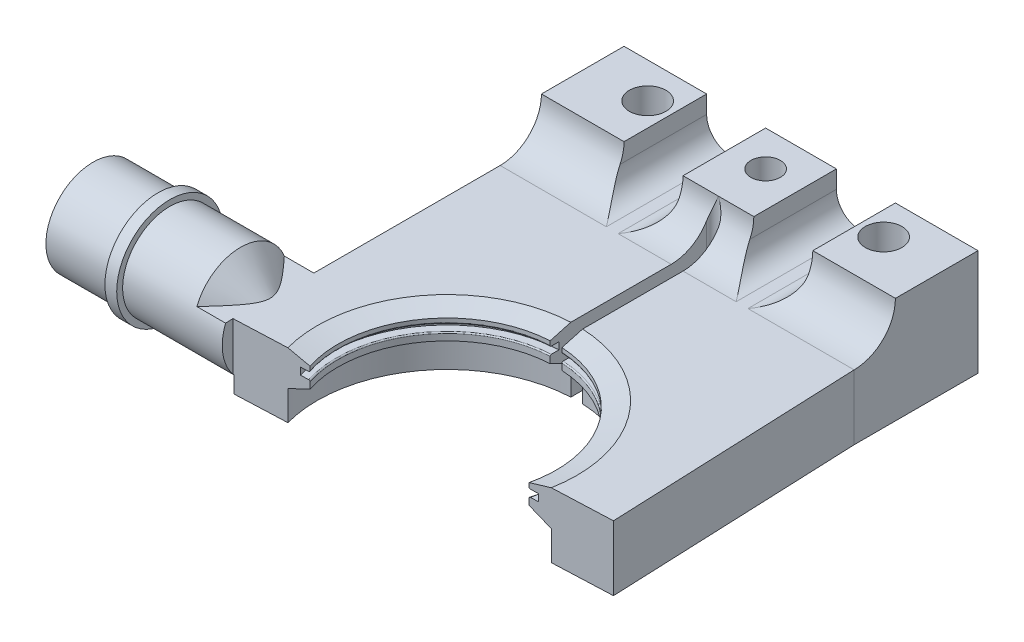
SolidWorks part; units mm, degrees
ref_plane "Front Plane" through (0, 0, 0) normal (0, 0, 1) x (1, 0, 0)
ref_plane "Top Plane" through (0, 0, 0) normal (0, 1, 0) x (1, 0, 0)
ref_plane "Right Plane" through (0, 0, 0) normal (1, 0, 0) x (0, 0, -1)
sketch "Sketch1" plane through (0, 0, 0) normal (0, 0, 1) x (1, 0, 0)
  line L0 (0, 0) -> (0, 15.868) construction
  line L1 (-20, -0.05) -> (-20, 1.15)
  line L2 (-20, 1.15) -> (-18.5, 1.15)
  line L3 (-18.5, 1.15) -> (-18.5, 2.0307)
  line L4 (-18.5, 2.0307) -> (-22, 3)
  line L5 (-22, 3) -> (-22, -3)
  line L6 (-22, -3) -> (-18.5, -1.3298)
  line L7 (-20, -0.05) -> (-18.5, -0.05)
  line L8 (-18.5, -0.05) -> (-18.5, -1.3298)
  point P13 (-20, 0.55)
  dimension "D1" = 1.5
  dimension "D2" = 18.5
  dimension "D3" = 3.5
  dimension "D4" = 0
  dimension "D5" = 3
  dimension "D6" = 3
  dimension "D7" = 1.2
  dimension "D8" = 74.521
  dimension "D9" = 64.49
revolve "Revolve1" add sketch "Sketch1" angle 360 about L0
sketch "Sketch2" plane through (0, 0, 0) normal (0, 1, 0) x (1, 0, 0)
  line L0 (0, 0) -> (-49.8042, -23.2241)
  line L1 (0, 0) -> (48.8836, -22.7948)
  line L2 (0, 0) -> (0, -13.7284) construction
  line L3 (-49.8042, -23.2241) -> (48.8836, -22.7948)
  dimension "D1" = 65
  dimension "D2" = 65
extrude "Cut-Extrude1" cut sketch "Sketch2" against normal through all and the other way through all
sketch "Sketch3" plane through (0, 0, 0) normal (0, 1, 0) x (1, 0, 0)
  line L0 (-30, -9.2976) -> (-30, 60)
  line L1 (-30, 60) -> (30, 60)
  line L2 (30, 60) -> (30, -9.2976)
  line L3 (-30, -9.2976) -> (-19.9388, -9.2976)
  line L4 (30, -9.2976) -> (19.9388, -9.2976)
  arc A0 (19.9388, -9.2976) -> (-19.9388, -9.2976) centre (0, 0) ccw
  circle A1 centre (0, 54) radius 2.5
  circle A2 centre (-20, 54) radius 3.1
  circle A3 centre (20, 54) radius 3.1
  arc A4 (19.9388, -9.2976) -> (-19.9388, -9.2976) centre (0, 0) ccw construction
  point P18 (0, 60)
  dimension "D8" = 6.2
  dimension "D9" = 6.2
  dimension "D10" = 5
  dimension "D2" = 20
  dimension "D3" = 6
  dimension "D4" = 60
  dimension "D5" = 20
  dimension "D6" = 60
extrude "Boss-Extrude1" add sketch "Sketch3" along normal blind 3 and the other way blind 8 contours L2 L1 L0 A3 A2 A1 region at (0, 0, -32.7973)
sketch "Sketch4" plane through (0, 0, 0) normal (0, 1, 0) x (1, 0, 0)
  line L0 (30, 60) -> (30, -9.2976) construction
  line L1 (-30, 60) -> (30, 60)
  line L2 (-30, 60) -> (-30, 46)
  line L3 (-30, 46) -> (30, 46)
  line L4 (30, 60) -> (30, 46)
  circle A0 centre (-20, 54) radius 3.1 construction
  circle A1 centre (-20, 54) radius 3.1
  circle A2 centre (0, 54) radius 2.5 construction
  circle A3 centre (0, 54) radius 2.5
  circle A4 centre (20, 54) radius 3.1 construction
  circle A5 centre (20, 54) radius 3.1
  dimension "D1" = 14
extrude "Boss-Extrude2" add sketch "Sketch4" along normal blind 10
fillet "Fillet1" radius 7 1 edges at (0, 3, -46)
sketch "Sketch5" plane through (0, 0, 0) normal (0, 1, 0) x (1, 0, 0)
  line L0 (0, 45) -> (0, -0.8023) construction
  line L1 (1, 45) -> (1, -0.8023)
  line L2 (-1, 45) -> (-1, -0.8023)
  arc A0 (1, 45) -> (-1, 45) centre (0, 45) ccw
  arc A1 (-1, -0.8023) -> (1, -0.8023) centre (0, -0.8023) ccw
  point P3 (0, 22.0988)
  dimension "D1" = 45
  dimension "D3" = 1
  dimension "D2" = 22.0988
extrude "Cut-Extrude2" cut sketch "Sketch5" against normal through all and the other way through all
sketch "Sketch6" plane through (0, 0, 0) normal (0, 1, 0) x (1, 0, 0)
  line L0 (30, 60) -> (-30, 60) construction
  line L1 (-4.1548, 72.2673) -> (4.1548, 72.2673)
  line L2 (-4.1548, 72.2673) -> (-4.1548, 47.7327)
  line L3 (-4.1548, 47.7327) -> (4.1548, 47.7327)
  line L4 (4.1548, 72.2673) -> (4.1548, 47.7327)
  line L5 (-4.1548, 72.2673) -> (4.1548, 47.7327) construction
  line L6 (-4.1548, 47.7327) -> (4.1548, 72.2673) construction
  point P0 (0, 60)
extrude "Cut-Extrude3" cut sketch "Sketch6" along normal blind 5
sketch "Sketch7" plane through (0, 0, 0) normal (0, 1, 0) x (1, 0, 0)
  line L1 (-16, 66.549) -> (-6, 66.549)
  line L2 (-16, 66.549) -> (-16, 20)
  line L3 (-16, 20) -> (-6, 20)
  line L4 (-6, 66.549) -> (-6, 20)
  line L6 (6, 66.549) -> (16, 66.549)
  line L7 (6, 66.549) -> (6, 20)
  line L8 (6, 20) -> (16, 20)
  line L9 (16, 66.549) -> (16, 20)
  point P6 (6, 43.2745)
  point P7 (-11, 20)
  dimension "D1" = 6
  dimension "D2" = 6
  dimension "D3" = 10
  dimension "D4" = 10
  dimension "D5" = 20
  dimension "D6" = 20
extrude "Cut-Extrude4" cut sketch "Sketch7" against normal blind 7 from offset 10
fillet "Fillet2" radius 4 4 edges at (6, 3, -49.5) (16, 3, -49.5) (-6, 3, -49.5) (-16, 3, -49.5)
fillet "Fillet3" radius 0.6 6 edges at (16.7667, 1.5904, 7.8184) (18.1262, 0.55, 8.4524) (16.7667, -0.6899, 7.8184) (-16.7667, -0.6899, 7.8184) (-16.7667, 1.5904, 7.8184) (-18.1262, 0.55, 8.4524)
sketch "Sketch9" plane through (0, 0, 0) normal (1, 0, 0) x (0, 0, -1)
  circle A0 centre (0, 0) radius 8
  point P2 (0, 0)
  dimension "D1" = 0
  dimension "D2" = 16
extrude "Boss-Extrude5" add sketch "Sketch9" against normal blind 30 from surface starting at face at (-30, 1.425, -31.3091)
chamfer "Chamfer2" distance 5 angle 45 1 edges at (-30, 8, 0)
sketch "Sketch12" plane through (0, 3, 0) normal (0, 1, 0) x (1, 0, 0)
  line L0 (30, 39) -> (32, -9.2976)
  line L1 (32, -9.2976) -> (30, -9.2976)
  line L2 (30, -9.2976) -> (30, 39)
  line L3 (30, 39) -> (12, 39) construction
  dimension "D1" = 2
extrude "Boss-Extrude8" add sketch "Sketch12" against normal up to surface (11 mm away) up to face at (20, -8, -50.9)
fillet "Fillet11" radius 0.2 12 edges at (-17.982, 1.15, 8.3851) (-16.995, 1.15, 7.7383) (-17.982, -0.05, 8.3851) (-16.995, -0.05, 7.7383) (17.982, 1.15, 8.3851) (16.995, 1.15, 7.7383) (17.982, -0.05, 8.3851) (16.995, -0.05, 7.7383) (-15.7144, 1.15, -9.7626) (-15.7144, -0.05, -9.7626) (15.7144, 1.15, -9.7626) (15.7144, -0.05, -9.7626)
sketch "Sketch15" plane through (-60, 0, 0) normal (-1, 0, 0) x (0, 0, 1)
  circle A0 centre (0, 0) radius 9
  circle A1 centre (0, 0) radius 8 construction
  dimension "D1" = 1
extrude "Boss-Extrude15" add sketch "Sketch15" against normal blind 2 from offset 11 offset against normal yes
sketch "Sketch17" plane through (31.5609, 0, -1.3069) normal (0.9991, 0, -0.0414) x (-0.0414, 0, -0.9991)
  line L5 (37.7254, -8) -> (-10.6136, -8) construction
  line L6 (-10.6136, 3) -> (-4.8636, 3)
  line L7 (-10.6136, 3) -> (-10.6136, -8)
  line L8 (-10.6136, -8) -> (-4.8636, -8)
  line L9 (-4.8636, 3) -> (-4.8636, -8)
  dimension "D1" = 5.75
extrude "Cut-Extrude6" cut sketch "Sketch17" against normal blind 62
